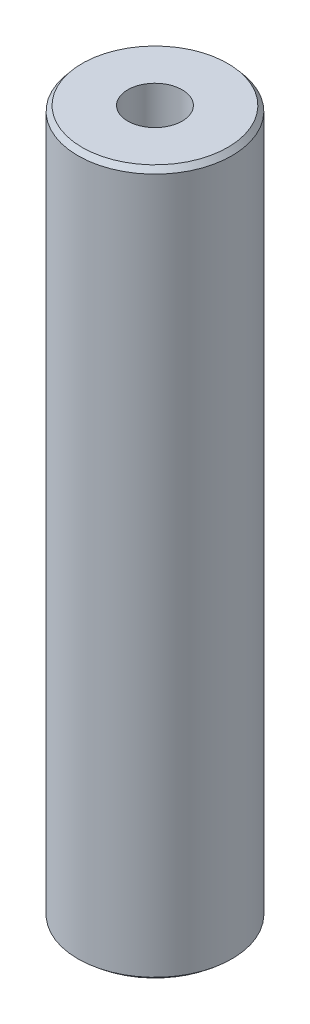
SolidWorks part; units mm, degrees
ref_plane "Front Plane" through (0, 0, 0) normal (0, 0, 1) x (1, 0, 0)
ref_plane "Top Plane" through (0, 0, 0) normal (0, 1, 0) x (1, 0, 0)
ref_plane "Right Plane" through (0, 0, 0) normal (1, 0, 0) x (0, 0, -1)
sketch "Sketch1" plane through (0, 0, 0) normal (0, 1, 0) x (1, 0, 0)
  circle A0 centre (0, 0) radius 22.5
  dimension "SHAFT_OD" = 45
extrude "Boss-Extrude1" add sketch "Sketch1" along normal blind 205.9548
sketch "Sketch2" plane through (0, 0, 0) normal (0, 1, 0) x (1, 0, 0)
  circle A0 centre (0, 0) radius 7.9488
  dimension "BORE_D" = 15.8976
extrude "Cut-Extrude1" cut sketch "Sketch2" along normal through all
chamfer "Chamfer1" distance 1.4873 angle 39.635 2 edges at (0, 205.9548, 22.5) (0, 0, 22.5) first distance on face at (0, 205.9548, 22.5) first distance on face at (0, 0, 7.9488)
